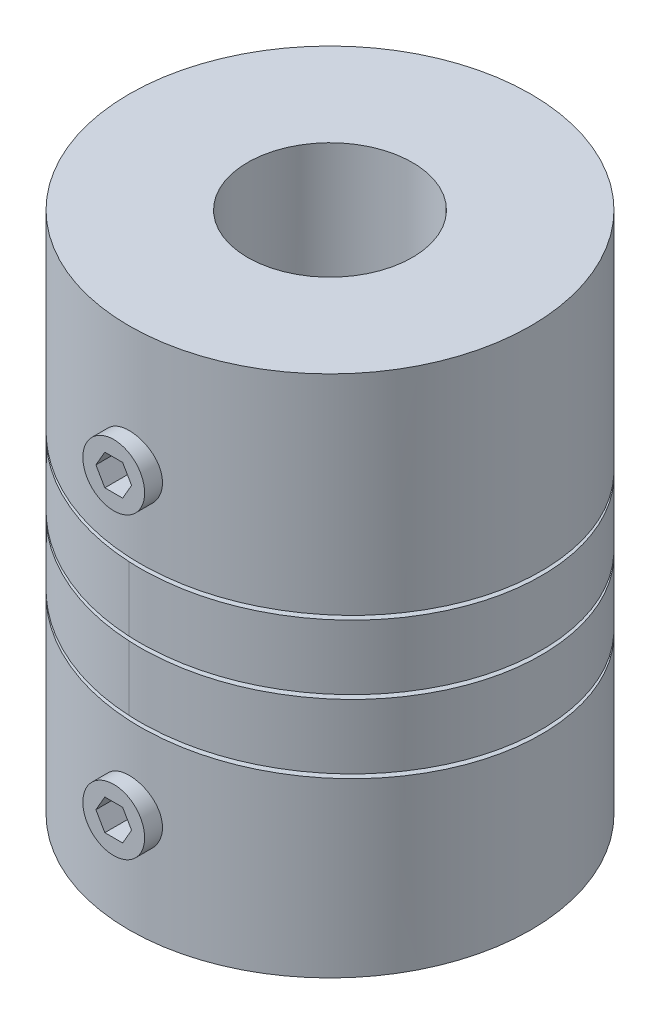
SolidWorks part; units mm, degrees
ref_plane "Front Plane" through (0, 0, 0) normal (0, 0, 1) x (1, 0, 0)
ref_plane "Top Plane" through (0, 0, 0) normal (0, 1, 0) x (1, 0, 0)
ref_plane "Right Plane" through (0, 0, 0) normal (1, 0, 0) x (0, 0, -1)
sketch "Sketch1" plane through (0, 0, 0) normal (0, 1, 0) x (1, 0, 0)
  circle A0 centre (0, 0) radius 9.75
extrude "Extrude1" add sketch "Sketch1" along normal blind 25.4
sketch "Sketch2" plane through (0, 25.4, 0) normal (0, 1, 0) x (-1, 0, 0)
  circle A0 centre (0, 0) radius 4
extrude "Extrude2" cut sketch "Sketch2" against normal blind 12.7
sketch "Sketch3" plane through (0, 0, 0) normal (0, -1, 0) x (1, 0, 0)
  circle A0 centre (0, 0) radius 2
extrude "Extrude3" cut sketch "Sketch3" against normal blind 12.7
ref_plane "Plane1" through (0, 0, 9.75) normal (0, 0, 1) x (1, 0, 0)
sketch "Sketch4" plane through (0, 0, 9.75) normal (0, 0, 1) x (1, 0, 0)
  circle A0 centre (0, 19.5) radius 1.5
  circle A1 centre (0, 5) radius 1.5
extrude "Extrude5" cut sketch "Sketch4" against normal blind 9.75
ref_plane "Plane2" through (0, 7.5, 0) normal (0, 1, 0) x (-1, 0, 0)
sketch "Sketch6" plane through (0, 7.5, 0) normal (0, 1, 0) x (-1, 0, 0)
  circle A0 centre (0, 0) radius 9.75
sketch "Sketch7" plane through (0, 7.5, 0) normal (0, 1, 0) x (-1, 0, 0)
  circle A0 centre (0, 0) radius 9.75
curve "Helix/Spiral2" pitch 3.3333 height 10 radius 9.75 left hand yes centre (0, 7.5, 0) axis (0, 1, 0) start towards (0, 0, -1)
sketch "Sketch10" plane through (0, 0, 0) normal (1, 0, 0) x (0, 0, -1)
  line L1 (10, 7.35) -> (1, 7.35)
  line L2 (10, 7.35) -> (10, 7.15)
  line L3 (10, 7.15) -> (1, 7.15)
  line L4 (1, 7.35) -> (1, 7.15)
sweep "Cut-Sweep8" cut profiles "Sketch10" path "Helix/Spiral2"
ref_plane "Plane3" through (0, 0, 7.5) normal (0, 0, 1) x (1, 0, 0)
sketch "Sketch11" plane through (0, 0, 7.5) normal (0, 0, 1) x (1, 0, 0)
  circle A0 centre (0, 19.5) radius 1.5
  circle A1 centre (0, 5) radius 1.5
extrude "Extrude6" add sketch "Sketch11" along normal blind 3 and the other way blind 3 separate body
sketch "Sketch12" plane through (0, 0, 10.5) normal (0, 0, 1) x (1, 0, 0)
  line L1 (0.866, 5) -> (0.433, 5.75)
  line L2 (0.433, 5.75) -> (-0.433, 5.75)
  line L3 (-0.433, 5.75) -> (-0.866, 5)
  line L4 (-0.866, 5) -> (-0.433, 4.25)
  line L5 (-0.433, 4.25) -> (0.433, 4.25)
  line L6 (0.433, 4.25) -> (0.866, 5)
  line L7 (0.866, 19.5) -> (0.433, 20.25)
  line L8 (0.433, 20.25) -> (-0.433, 20.25)
  line L9 (-0.433, 20.25) -> (-0.866, 19.5)
  line L10 (-0.866, 19.5) -> (-0.433, 18.75)
  line L11 (-0.433, 18.75) -> (0.433, 18.75)
  line L12 (0.433, 18.75) -> (0.866, 19.5)
  circle A0 centre (0, 5) radius 0.75 construction
  circle A1 centre (0, 19.5) radius 0.75 construction
extrude "Extrude7" cut sketch "Sketch12" against normal blind 3
